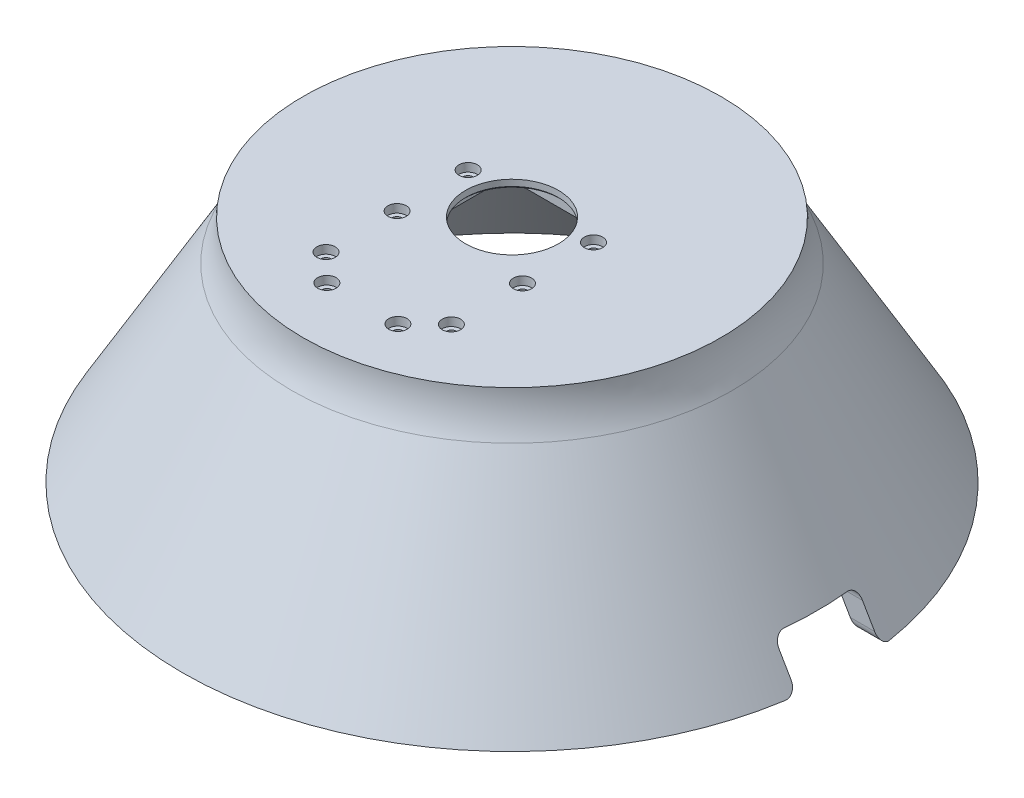
SolidWorks part; units mm, degrees
ref_plane "Front Plane" through (0, 0, 0) normal (0, 0, 1) x (1, 0, 0)
ref_plane "Top Plane" through (0, 0, 0) normal (0, 1, 0) x (1, 0, 0)
ref_plane "Right Plane" through (0, 0, 0) normal (1, 0, 0) x (0, 0, -1)
sketch "Sketch1" plane through (0, 0, 0) normal (0, 1, 0) x (1, 0, 0)
  circle A0 centre (0, 0) radius 50
  dimension "D1" = 100
extrude "Boss-Extrude1" add sketch "Sketch1" along normal blind 5
sketch "Sketch2" plane through (0, 0, 0) normal (0, -1, 0) x (1, 0, 0)
  circle A0 centre (0, 0) radius 50
  circle A1 centre (0, 0) radius 50 construction
extrude "Boss-Extrude2" add sketch "Sketch2" along normal blind 50 draft 30 draft outward yes
fillet "Fillet1" radius 20 1 edges at (0, 0, -50)
shell "Shell1" thickness 5 removed face at (0, -50, -78.8675)
sketch "Sketch3" plane through (0, 0, 0) normal (1, 0, 0) x (0, 0, -1)
  line L0 (-78.8675, -50) -> (78.8675, -50) construction
  line L2 (-10, -60) -> (10, -60)
  line L3 (-10, -60) -> (-10, -40)
  line L4 (-10, -40) -> (10, -40)
  line L5 (10, -60) -> (10, -40)
  line L6 (-10, -60) -> (10, -40) construction
  line L7 (-10, -40) -> (10, -60) construction
  point P0 (0, -50)
  point P1 (0, -50)
  dimension "D1" = 20
  dimension "D2" = 20
extrude "Cut-Extrude1" cut sketch "Sketch3" against normal through all both and the other way through all
fillet "Fillet2" radius 2.5 8 edges at (75.3188, -50, 10) (69.4902, -40, 10) (75.3188, -50, -10) (69.4902, -40, -10) (-75.3188, -50, 10) (-69.4902, -40, 10) (-75.3188, -50, -10) (-69.4902, -40, -10)
sketch "Sketch4" plane through (0, 5, 0) normal (0, 1, 0) x (1, 0, 0)
  line L10 (-17.0858, -33.4402) -> (-13.5985, -37.5429)
  line L11 (-11.3127, -38.6) -> (11.3127, -38.6)
  line L12 (13.5985, -37.5429) -> (17.0858, -33.4402)
  line L13 (17.8, -31.4973) -> (17.8, 4.8973)
  line L14 (17.0858, 6.8402) -> (13.5985, 10.9429)
  line L15 (11.3127, 12) -> (9.2, 12)
  line L16 (9.2, 12) -> (-9.2, 12)
  line L17 (-9.2, 12) -> (-11.3127, 12)
  line L18 (-13.5985, 10.9429) -> (-17.0858, 6.8402)
  line L19 (-17.8, 4.8973) -> (-17.8, -31.4973)
  line L20 (0, -1.9432) -> (0, -50001.9432) construction
  line L21 (12.2, -30) -> (12.2, 9)
  line L22 (-9.2, -33) -> (9.2, -33)
  line L23 (-12.2, 9) -> (-12.2, -30)
  circle A26 centre (-276.7561, -35.8) radius 1.025
  circle A27 centre (0, 0) radius 4
  circle A28 centre (0, 0) radius 11
  circle A29 centre (0, 8) radius 1
  circle A30 centre (5.6569, 5.6569) radius 1
  circle A31 centre (8, 0) radius 1
  circle A32 centre (5.6569, -5.6569) radius 1
  circle A33 centre (0, -8) radius 1
  circle A34 centre (-5.6569, -5.6569) radius 1
  circle A35 centre (-8, 0) radius 1
  circle A36 centre (-5.6569, 5.6569) radius 1
  arc A37 (-17.8, -31.4973) -> (-17.0858, -33.4402) centre (-14.8, -31.4973) ccw
  arc A38 (-13.5985, -37.5429) -> (-11.3127, -38.6) centre (-11.3127, -35.6) ccw
  arc A39 (11.3127, -38.6) -> (13.5985, -37.5429) centre (11.3127, -35.6) ccw
  arc A40 (17.0858, -33.4402) -> (17.8, -31.4973) centre (14.8, -31.4973) ccw
  arc A41 (17.8, 4.8973) -> (17.0858, 6.8402) centre (14.8, 4.8973) ccw
  arc A42 (13.5985, 10.9429) -> (11.3127, 12) centre (11.3127, 9) ccw
  arc A43 (-11.3127, 12) -> (-13.5985, 10.9429) centre (-11.3127, 9) ccw
  arc A44 (-17.0858, 6.8402) -> (-17.8, 4.8973) centre (-14.8, 4.8973) ccw
  circle A45 centre (-15, 4.5) radius 1.025
  circle A46 centre (-15, -12.5) radius 1.025
  circle A47 centre (-15, -29.5) radius 1.025
  circle A48 centre (-8.5, -35.8) radius 1.025
  circle A49 centre (-270.2561, -29.5) radius 1.025
  circle A50 centre (-270.2561, -12.5) radius 1.025
  circle A51 centre (-270.2561, 4.5) radius 1.025
  arc A52 (12.2, 9) -> (9.2, 12) centre (9.2, 9) ccw
  arc A53 (9.2, -33) -> (12.2, -30) centre (9.2, -30) ccw
  arc A54 (-12.2, -30) -> (-9.2, -33) centre (-9.2, -30) ccw
  arc A55 (-9.2, 12) -> (-12.2, 9) centre (-9.2, 9) ccw
  circle A56 centre (8.5, -35.8) radius 1.025
  circle A57 centre (15, -29.5) radius 1.025
  circle A58 centre (15, -12.5) radius 1.025
  circle A59 centre (15, 4.5) radius 1.025
  point P21 (0, 0)
sketch "Sketch5" plane through (0, 5, 0) normal (0, 1, 0) x (1, 0, 0)
  circle A2 centre (0, 0) radius 11.1
  circle A3 centre (0, 0) radius 11.1
  dimension "D1" = 0.1
extrude "Cut-Extrude3" cut sketch "Sketch5" against normal through all both
sketch "Sketch7" plane through (0, 0, 0) normal (0, -1, 0) x (1, 0, 0)
  line L20 (-13.6747, 37.6077) -> (-17.162, 33.505)
  line L21 (11.3127, 38.7) -> (-11.3127, 38.7)
  line L22 (17.162, 33.505) -> (13.6747, 37.6077)
  line L23 (17.9, -4.8973) -> (17.9, 31.4973)
  line L24 (13.6747, -11.0077) -> (17.162, -6.905)
  line L25 (9.2, -12.1) -> (11.3127, -12.1)
  line L26 (-9.2, -12.1) -> (9.2, -12.1)
  line L27 (-11.3127, -12.1) -> (-9.2, -12.1)
  line L28 (-17.162, -6.905) -> (-13.6747, -11.0077)
  line L29 (-17.9, 31.4973) -> (-17.9, -4.8973)
  line L30 (-13.6747, 37.6077) -> (-17.162, 33.505)
  line L31 (11.3127, 38.7) -> (-11.3127, 38.7)
  line L32 (17.162, 33.505) -> (13.6747, 37.6077)
  line L33 (17.9, -4.8973) -> (17.9, 31.4973)
  line L34 (13.6747, -11.0077) -> (17.162, -6.905)
  line L35 (9.2, -12.1) -> (11.3127, -12.1)
  line L36 (-9.2, -12.1) -> (9.2, -12.1)
  line L37 (-11.3127, -12.1) -> (-9.2, -12.1)
  line L38 (-17.162, -6.905) -> (-13.6747, -11.0077)
  line L39 (-17.9, 31.4973) -> (-17.9, -4.8973)
  arc A16 (-11.3127, 38.7) -> (-13.6747, 37.6077) centre (-11.3127, 35.6) ccw
  arc A17 (13.6747, 37.6077) -> (11.3127, 38.7) centre (11.3127, 35.6) ccw
  arc A18 (17.9, 31.4973) -> (17.162, 33.505) centre (14.8, 31.4973) ccw
  arc A19 (17.162, -6.905) -> (17.9, -4.8973) centre (14.8, -4.8973) ccw
  arc A20 (11.3127, -12.1) -> (13.6747, -11.0077) centre (11.3127, -9) ccw
  arc A21 (-13.6747, -11.0077) -> (-11.3127, -12.1) centre (-11.3127, -9) ccw
  arc A22 (-17.9, -4.8973) -> (-17.162, -6.905) centre (-14.8, -4.8973) ccw
  arc A23 (-17.162, 33.505) -> (-17.9, 31.4973) centre (-14.8, 31.4973) ccw
  arc A24 (-11.3127, 38.7) -> (-13.6747, 37.6077) centre (-11.3127, 35.6) ccw
  arc A25 (13.6747, 37.6077) -> (11.3127, 38.7) centre (11.3127, 35.6) ccw
  arc A26 (17.9, 31.4973) -> (17.162, 33.505) centre (14.8, 31.4973) ccw
  arc A27 (17.162, -6.905) -> (17.9, -4.8973) centre (14.8, -4.8973) ccw
  arc A28 (11.3127, -12.1) -> (13.6747, -11.0077) centre (11.3127, -9) ccw
  arc A29 (-13.6747, -11.0077) -> (-11.3127, -12.1) centre (-11.3127, -9) ccw
  arc A30 (-17.9, -4.8973) -> (-17.162, -6.905) centre (-14.8, -4.8973) ccw
  arc A31 (-17.162, 33.505) -> (-17.9, 31.4973) centre (-14.8, 31.4973) ccw
  dimension "D1" = 0.1
extrude "Cut-Extrude4" cut sketch "Sketch7" against normal blind 1
sketch "Sketch9" plane through (0, 0, 0) normal (0, -1, 0) x (1, 0, 0)
  line L13 (12.3, -9) -> (12.3, 30)
  line L14 (-9.2, -12.1) -> (9.2, -12.1)
  line L15 (-12.3, 30) -> (-12.3, -9)
  line L16 (9.2, 33.1) -> (-9.2, 33.1)
  line L17 (12.3, -9) -> (12.3, 30)
  line L18 (-9.2, -12.1) -> (9.2, -12.1)
  line L19 (-12.3, 30) -> (-12.3, -9)
  line L20 (9.2, 33.1) -> (-9.2, 33.1)
  arc A17 (12.3, 30) -> (9.2, 33.1) centre (9.2, 30) ccw
  arc A18 (9.2, -12.1) -> (12.3, -9) centre (9.2, -9) ccw
  arc A19 (-12.3, -9) -> (-9.2, -12.1) centre (-9.2, -9) ccw
  arc A20 (-9.2, 33.1) -> (-12.3, 30) centre (-9.2, 30) ccw
  arc A21 (12.3, 30) -> (9.2, 33.1) centre (9.2, 30) ccw
  arc A22 (9.2, -12.1) -> (12.3, -9) centre (9.2, -9) ccw
  arc A23 (-12.3, -9) -> (-9.2, -12.1) centre (-9.2, -9) ccw
  arc A24 (-9.2, 33.1) -> (-12.3, 30) centre (-9.2, 30) ccw
  dimension "D1" = 0.1
extrude "Cut-Extrude5" cut sketch "Sketch9" against normal blind 3
chamfer "Chamfer1" distance 0.5 angle 45 23 edges at (11.392, 1, -11.192) (12.3, 1, 10.5) (11.392, 1, 32.192) (-11.392, 1, -11.192) (0, 1, 33.1) (-12.3, 1, 10.5) (-11.392, 1, 32.192) (17.9, 0, 13.3) (17.7097, 0, 32.5668) (17.7097, 0, -5.9668) (15.4184, 0, 35.5563) (15.4184, 0, -8.9563) (12.6139, 0, 38.4137) (12.6139, 0, -11.8137) (0, 0, 38.7) (0, 0, -12.1) (-12.6139, 0, 38.4137) (-12.6139, 0, -11.8137) (-15.4184, 0, 35.5563) (-15.4184, 0, -8.9563) (-17.7097, 0, 32.5668) (-17.7097, 0, -5.9668) (-17.9, 0, 13.3)
hole_wizard "CBORE for M2 SHCS1" positions "3DSketch2" profile "Sketch11" counterbore size "M2" standard "ANSI Metric"
sketch3d "3DSketch2"
  point P0 (-15, 5, 12.5)
  point P3 (-15, 5, 29.5)
  point P6 (15, 5, 29.5)
  point P9 (15, 5, 12.5)
  point P12 (15, 5, -4.5)
  point P15 (-15, 5, -4.5)
  point P18 (-8.5, 5, 35.8)
  point P21 (8.5, 5, 35.8)
sketch "Sketch11" plane through (-15, 5, 12.5) normal (1, 0, 0) x (0, 0, 1)
  line L0 (0, 0) -> (0, 8.721)
  line L1 (0, 8.721) -> (1.2, 8)
  line L2 (1.2, 8) -> (1.2, 2)
  line L3 (1.2, 2) -> (2.2, 2)
  line L4 (2.2, 2) -> (2.2, 0)
  line L5 (2.2, 0) -> (0, 0)
  line L10 (0, 8.721) -> (-1.2, 8) construction
  line L11 (0, -6.35) -> (0, 107.95) construction
  dimension "Hole Dia." = 2.4
  dimension "Hole Depth" = 8
  dimension "C'Bore Dia." = 4.4
  dimension "C'Bore Depth" = 2
  dimension "Drill Angle" = 118
chamfer "Chamfer2" distance 0.5 angle 45 1 edges at (0, 3, -11.1)
